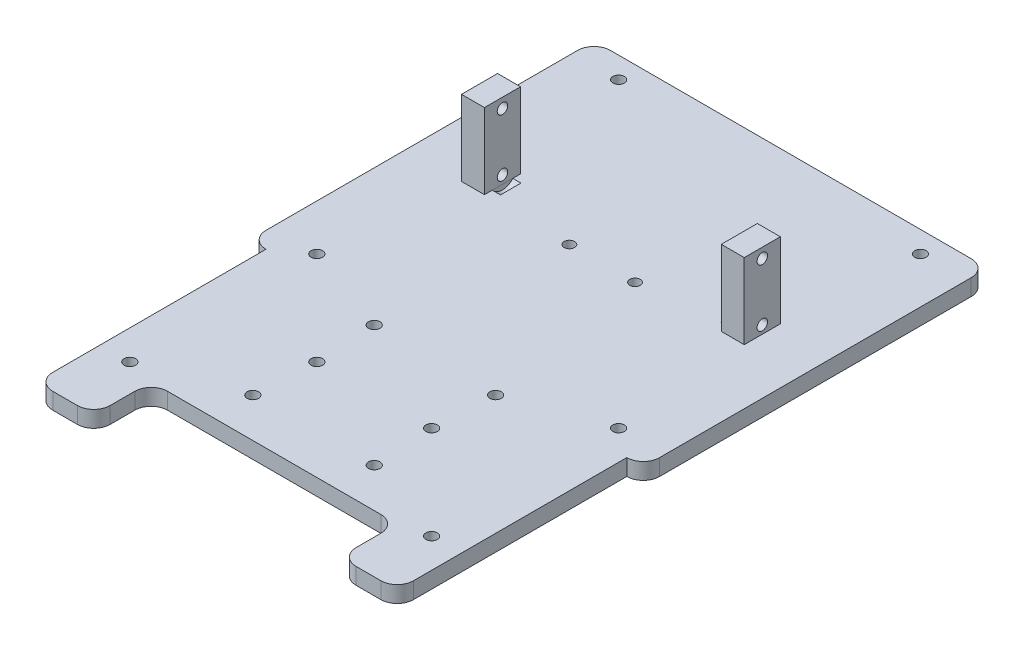
SolidWorks part; units mm, degrees
ref_plane "정면" through (0, 0, 0) normal (0, 0, 1) x (1, 0, 0)
ref_plane "윗면" through (0, 0, 0) normal (0, 1, 0) x (1, 0, 0)
ref_plane "우측면" through (0, 0, 0) normal (1, 0, 0) x (0, 0, -1)
sketch "스케치1" plane through (0, 0, 0) normal (0, 1, 0) x (1, 0, 0)
  line L0 (-55, -52.5) -> (-60, -52.5)
  line L1 (60, 52.5) -> (-60, 52.5)
  line L2 (60, 52.5) -> (60, -52.5)
  line L3 (60, -52.5) -> (55, -52.5)
  line L4 (-60, 52.5) -> (-60, -52.5)
  line L5 (60, 52.5) -> (-60, -52.5) construction
  line L6 (60, -52.5) -> (-60, 52.5) construction
  line L7 (55, -122.5) -> (-55, -122.5)
  line L8 (55, -122.5) -> (55, -52.5)
  line L10 (-55, -122.5) -> (-55, -52.5)
  line L11 (55, -122.5) -> (-55, -52.5) construction
  line L12 (55, -52.5) -> (-55, -122.5) construction
  point P0 (0, 0)
  point P6 (0, -87.5)
  dimension "D1" = 120
  dimension "D2" = 105
  dimension "D3" = 110
  dimension "D4" = 70
extrude "보스-돌출1" add sketch "스케치1" along normal blind 5
sketch "스케치2" plane through (0, 5, 0) normal (0, 1, 0) x (1, 0, 0)
  line L0 (-43.1, 29.5) -> (-43.1, -5.3) construction
  line L1 (-36.1, -4.8) -> (-43.1, -4.8)
  line L2 (-36.1, -4.8) -> (-36.1, 6.2)
  line L3 (-36.1, 6.2) -> (-43.1, 6.2)
  line L4 (-43.1, -4.8) -> (-43.1, 6.2)
  line L5 (-61.9, -0.8) -> (-43.1, -0.8) construction
  line L6 (-43.1, 2.2) -> (-61.9, 2.2) construction
  dimension "D1" = 7
  dimension "D2" = 4
  dimension "D3" = 4
extrude "보스-돌출2" add sketch "스케치2" along normal blind 23 separate body
sketch "스케치3" plane through (-36.1, 0, 0) normal (1, 0, 0) x (0, 0, -1)
  circle A0 centre (0.7, 7.5) radius 1.5 construction
  circle A1 centre (0.7, 25) radius 1.5 construction
  circle A2 centre (0.7, 25) radius 1.6
  circle A3 centre (0.7, 7.5) radius 1.6
  circle A4 centre (0.7, 7.5) radius 1.5 construction
  circle A5 centre (0.7, 25) radius 1.5 construction
  dimension "D1" = 3.2
  dimension "D2" = 3.2
extrude "컷-돌출1" cut sketch "스케치3" against normal through all
mirror "대칭 복사1" about plane through (0, 0, 0) normal (1, 0, 0) of bodies 103
sketch "스케치5" plane through (0, 5, 0) normal (0, 1, 0) x (1, 0, 0)
  circle A0 centre (-46, -46) radius 1.75 construction
  circle A1 centre (-46, 46) radius 1.75 construction
  circle A2 centre (46, 46) radius 1.75 construction
  circle A3 centre (46, -46) radius 1.75 construction
  circle A4 centre (-46, -46) radius 1.75
  circle A5 centre (-46, 46) radius 1.75
  circle A6 centre (46, 46) radius 1.75
  circle A7 centre (46, -46) radius 1.75
extrude "메인보드 홀" cut sketch "스케치5" against normal through all
sketch "Sketch2" plane through (36.1, 0, 0) normal (-1, 0, 0) x (0, 0, 1)
  circle A0 centre (-0.7, 7.5) radius 4
  dimension "D1" = 8
extrude "Cut-Extrude1" cut sketch "Sketch2" along normal blind 2.5
sketch "Sketch3" plane through (-36.1, 0, 0) normal (1, 0, 0) x (0, 0, -1)
  circle A0 centre (0.7, 7.5) radius 4
  dimension "D1" = 8
extrude "Cut-Extrude2" cut sketch "Sketch3" along normal blind 2.5
sketch "Sketch4" plane through (0, 5, 0) normal (0, 1, 0) x (1, 0, 0)
  circle A0 centre (10, -5) radius 1.5 construction
  circle A1 centre (-10, -5) radius 1.5 construction
  circle A2 centre (10, -5) radius 1.5 construction
  circle A3 centre (-10, -5) radius 1.5 construction
  circle A4 centre (-10, -5) radius 1.6
  circle A5 centre (10, -5) radius 1.6
  dimension "D1" = 3.2
  dimension "D2" = 3.2
extrude "배터리홀더 홀" cut sketch "Sketch4" against normal through all and the other way through all
sketch "Sketch6" plane through (0, 5, 0) normal (0, 1, 0) x (1, 0, 0)
  line L1 (-18.5, -93) -> (18.5, -93) construction
  line L2 (-18.5, -93) -> (-18.5, -56) construction
  line L3 (-18.5, -56) -> (18.5, -56) construction
  line L4 (18.5, -93) -> (18.5, -56) construction
  line L5 (-18.5, -93) -> (18.5, -56) construction
  line L6 (-18.5, -56) -> (18.5, -93) construction
  circle A0 centre (-46, -46) radius 1.75 construction
  circle A1 centre (-18.5, -93) radius 1.75
  circle A2 centre (-18.5, -56) radius 1.75
  circle A3 centre (18.5, -56) radius 1.75
  circle A4 centre (18.5, -93) radius 1.75
  point P0 (0, -74.5)
  dimension "D3" = 3.5
  dimension "D1" = 37
  dimension "D2" = 10
extrude "모터드라이버 홀" cut sketch "Sketch6" against normal through all
sketch "Sketch7" plane through (0, 5, 0) normal (0, 1, 0) x (1, 0, 0)
  line L0 (-46, -103) -> (46, -103) construction
  line L1 (0, -103) -> (0, 0) construction
  circle A0 centre (-46, -103) radius 1.75
  circle A1 centre (-18.5, -93) radius 1.75 construction
  circle A2 centre (46, -103) radius 1.75
  point P6 (0, -103)
  point P13 (-37.9503, -103)
  dimension "D1" = 3.5
  dimension "D3" = 3.5
  dimension "D2" = 10
  dimension "D4" = 92
extrude "센서보드 홀" cut sketch "Sketch7" against normal through all
sketch "Sketch9" plane through (0, 5, 0) normal (0, 1, 0) x (1, 0, 0)
  line L0 (-17.5, -74.5) -> (17.5, -74.5) construction
  circle A0 centre (-17.5, -74.5) radius 1.75
  circle A1 centre (17.5, -74.5) radius 1.75
  dimension "D2" = 3.5
  dimension "D1" = 35
extrude "볼캐스터 홀" cut sketch "Sketch9" against normal through all
sketch "Sketch8" plane through (0, 5, 0) normal (0, 1, 0) x (1, 0, 0)
  line L0 (-55, -122.5) -> (55, -122.5) construction
  line L1 (-37.5, -140) -> (37.5, -140)
  line L2 (-37.5, -140) -> (-37.5, -105)
  line L3 (-37.5, -105) -> (37.5, -105)
  line L4 (37.5, -140) -> (37.5, -105)
  line L5 (-37.5, -140) -> (37.5, -105) construction
  line L6 (-37.5, -105) -> (37.5, -140) construction
  point P0 (0, -122.5)
  point P7 (0, 0)
  dimension "D1" = 75
  dimension "D2" = 35
extrude "Cut-Extrude7" cut sketch "Sketch8" against normal through all
fillet "필렛1" radius 5 8 edges at (60, 2.5, -52.5) (-60, 2.5, -52.5) (55, 2.5, 122.5) (-55, 2.5, 122.5) (37.5, 2.5, 122.5) (-37.5, 2.5, 122.5) (37.5, 2.5, 105) (-37.5, 2.5, 105)
fillet "Fillet2" radius 5 2 edges at (60, 2.5, 52.5) (-60, 2.5, 52.5)
